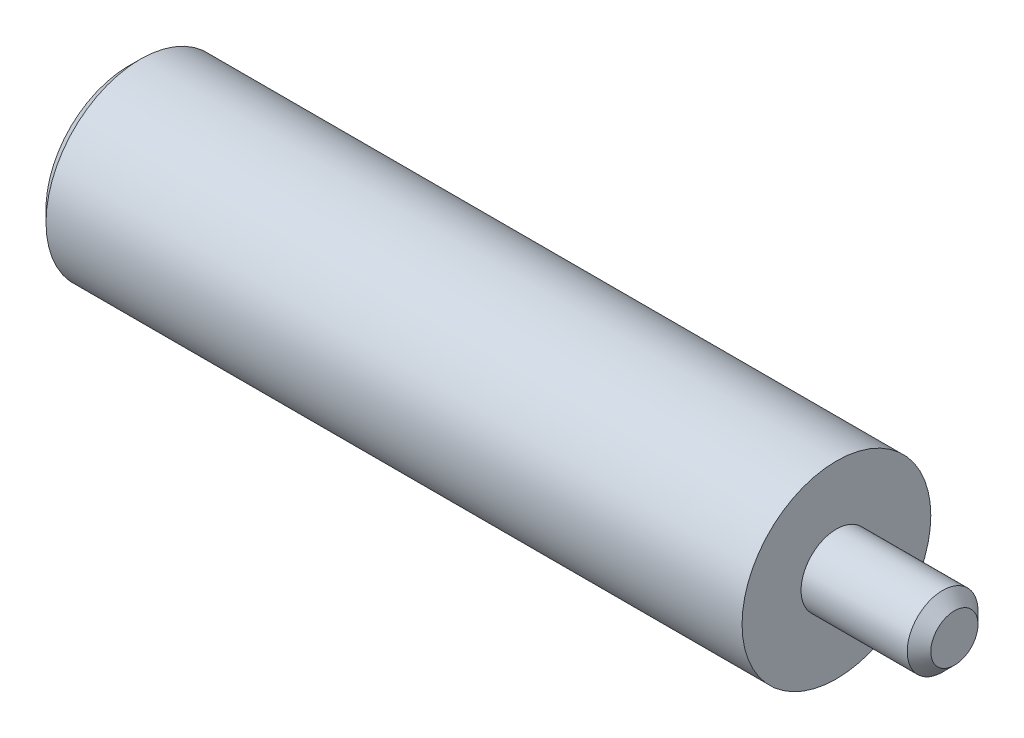
SolidWorks part; units mm, degrees
ref_plane "Alzado" through (0, 0, 0) normal (0, 0, 1) x (1, 0, 0)
ref_plane "Planta" through (0, 0, 0) normal (0, 1, 0) x (1, 0, 0)
ref_plane "Vista lateral" through (0, 0, 0) normal (1, 0, 0) x (0, 0, -1)
sketch "Croquis1" plane through (0, 0, 0) normal (1, 0, 0) x (0, 0, -1)
  circle A0 centre (0, 0) radius 4
  dimension "D1" = 8
extrude "Saliente-Extruir1" add sketch "Croquis1" along normal blind 30
sketch "Croquis2" plane through (30, 0, 0) normal (1, 0, 0) x (0, 0, -1)
  circle A0 centre (0, 0) radius 1.5
  dimension "D1" = 3
extrude "Saliente-Extruir2" add sketch "Croquis2" along normal blind 5
cosmetic thread "Rosca cosmética1" parameters "D2"=2
chamfer "Chaflán1" distance 0.5 angle 45 1 edges at (0, 0, -4)
chamfer "Chaflán2" distance 0.5 angle 45 1 edges at (35, 0, -1.5)
